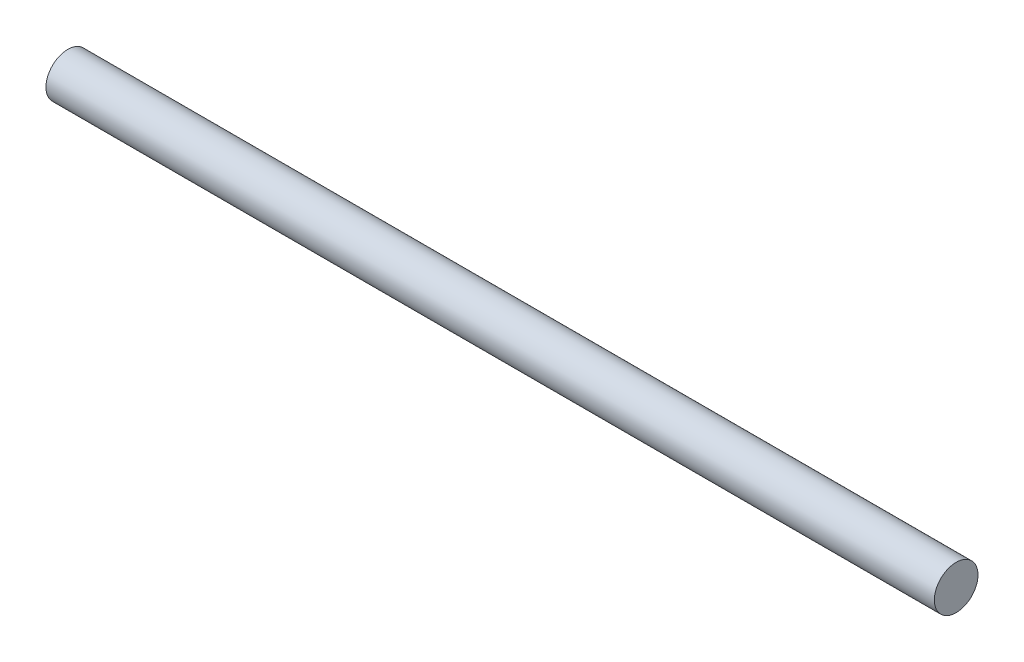
SolidWorks part; units mm, degrees
material "AISI 304"
ref_plane "Front Plane" through (0, 0, 0) normal (0, 0, 1) x (1, 0, 0)
ref_plane "Top Plane" through (0, 0, 0) normal (0, 1, 0) x (1, 0, 0)
ref_plane "Right Plane" through (0, 0, 0) normal (1, 0, 0) x (0, 0, -1)
sketch "Sketch1" plane through (0, 0, 0) normal (1, 0, 0) x (0, 0, -1)
  circle A0 centre (0, 0) radius 1.229
  dimension "D1" = 2.458
extrude "Extrude1" add sketch "Sketch1" along normal blind 25 and the other way blind 25
